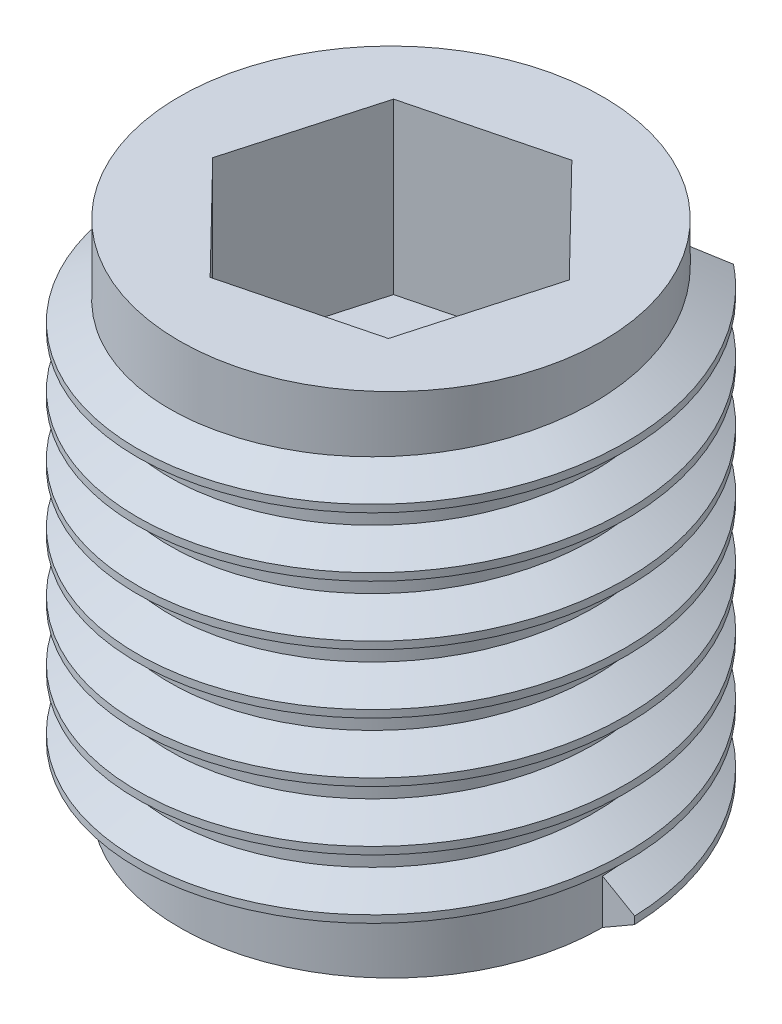
SolidWorks part; units mm, degrees
ref_plane "Ön Düzlem" through (0, 0, 0) normal (0, 0, 1) x (1, 0, 0)
ref_plane "Üst Düzlem" through (0, 0, 0) normal (0, 1, 0) x (1, 0, 0)
ref_plane "Sağ Düzlem" through (0, 0, 0) normal (1, 0, 0) x (0, 0, -1)
sketch "Çizim1" plane through (0, 0, 0) normal (0, 1, 0) x (1, 0, 0)
  circle A0 centre (0, 0) radius 2.5
  dimension "D1" = 5
extrude "Yükseklik-Ekstrüzyon1" add sketch "Çizim1" along normal blind 6
sketch "Çizim2" plane through (0, 6, 0) normal (0, 1, 0) x (1, 0, 0)
  line L1 (1.2095, -1.2398) -> (1.6784, 0.4276)
  line L2 (1.6784, 0.4276) -> (0.4689, 1.6674)
  line L3 (0.4689, 1.6674) -> (-1.2095, 1.2398)
  line L4 (-1.2095, 1.2398) -> (-1.6784, -0.4276)
  line L5 (-1.6784, -0.4276) -> (-0.4689, -1.6674)
  line L6 (-0.4689, -1.6674) -> (1.2095, -1.2398)
  circle A0 centre (0, 0) radius 1.5 construction
  dimension "D1" = 3
extrude "Kes-Ekstrüzyon1" cut sketch "Çizim2" against normal blind 2
thread "Diş1" pitch 0.7 method extrude profile "Diş Profili1" start angle 0, offset 0, length 5, pitch 0.7, diameter 5
ref_plane "Düzlem1" through (2.5, 0, 0) normal (0, 0, 1) x (1, 0, 0)
sketch "Diş Profili1" plane through (2.5, 0, 0) normal (0, 0, 1) x (1, 0, 0)
  line L0 (0, 0) -> (0, 0.7) construction
  line L1 (0, 0) -> (0.3789, 0.2187)
  line L2 (0.3789, 0.2187) -> (0.3789, 0.3062)
  line L3 (0.3789, 0.3062) -> (0, 0.525)
  line L4 (0.3789, 0.2625) -> (0, 0.2625) construction
  line L11 (0, 0) -> (0, 0.525)
  point P2 (0, 0)
  dimension "Pitch" = 0.7
  dimension "Profile_Angle" = 60
  dimension "Profile_Land" = 0.0875
  dimension "Profile_Height" = 0.3789
